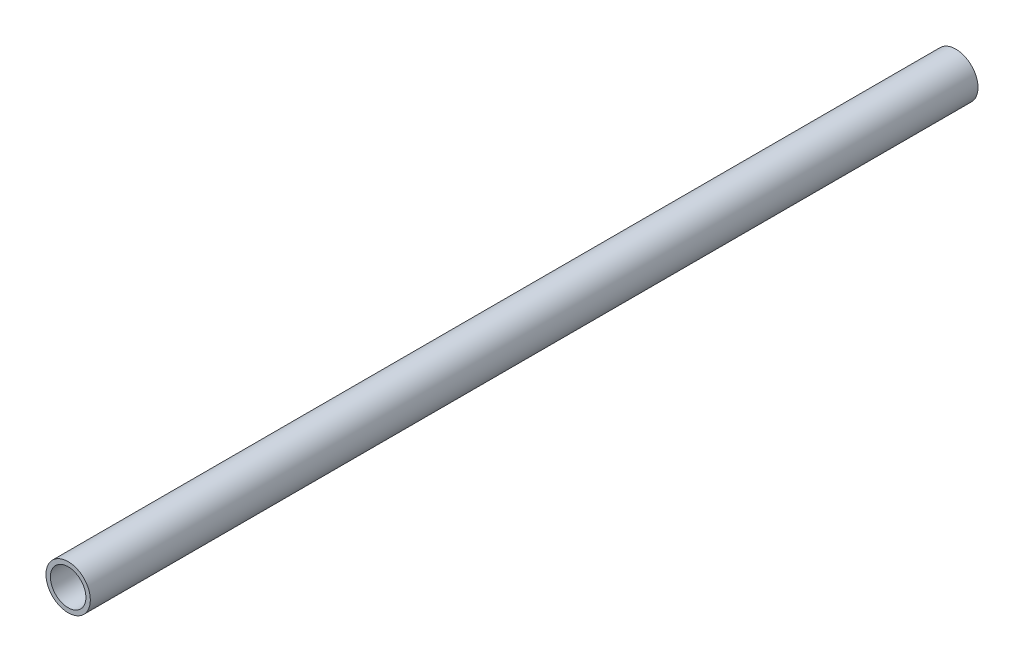
SolidWorks part; units mm, degrees
ref_plane "Front Plane" through (0, 0, 0) normal (0, 0, 1) x (1, 0, 0)
ref_plane "Top Plane" through (0, 0, 0) normal (0, 1, 0) x (1, 0, 0)
ref_plane "Right Plane" through (0, 0, 0) normal (1, 0, 0) x (0, 0, -1)
sketch "Sketch1" plane through (0, 0, 0) normal (0, 0, 1) x (1, 0, 0)
  circle A0 centre (0, 0) radius 10
  circle A1 centre (0, 0) radius 8
extrude "Boss-Extrude1" add sketch "Sketch1" along normal blind 400
ref_axis "Axis1" through (0, 0, 400) along (0, 0, -1)
